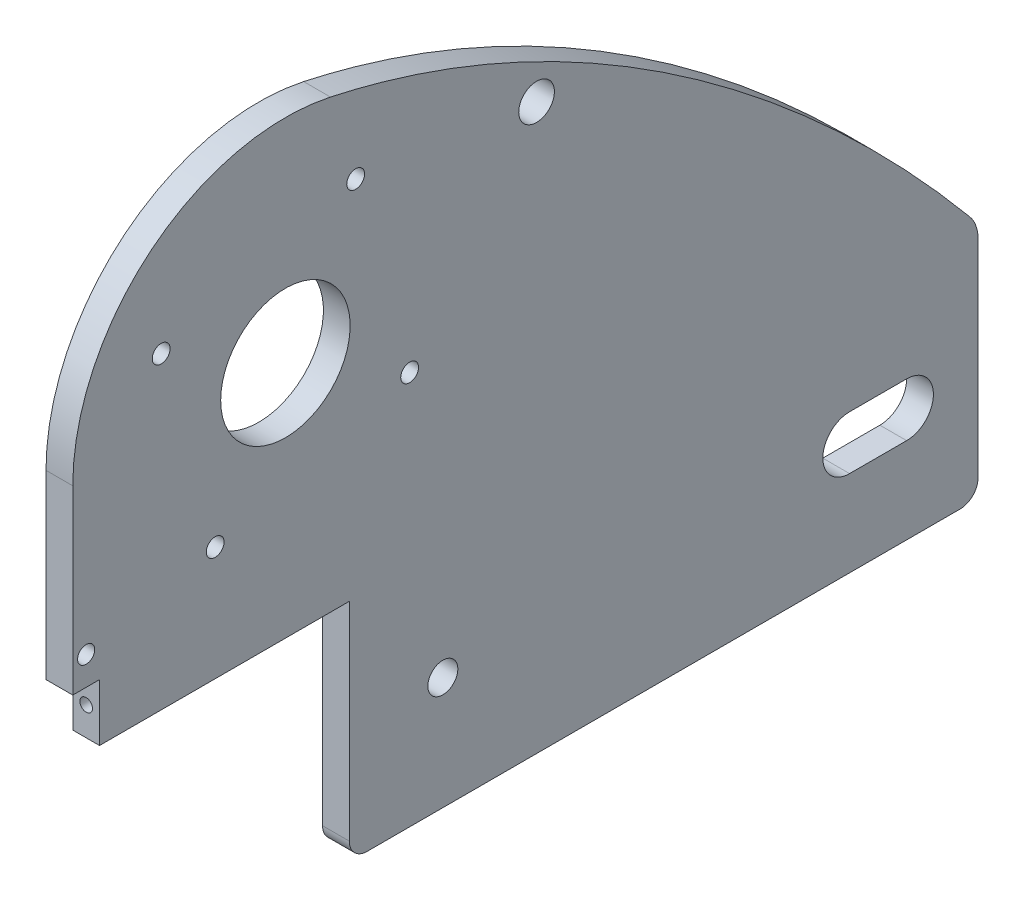
SolidWorks part; units mm, degrees
ref_plane "Front Plane" through (0, 0, 0) normal (0, 0, 1) x (1, 0, 0)
ref_plane "Top Plane" through (0, 0, 0) normal (0, 1, 0) x (1, 0, 0)
ref_plane "Right Plane" through (0, 0, 0) normal (1, 0, 0) x (0, 0, -1)
sketch "Sketch1" plane through (0, 0, 0) normal (1, 0, 0) x (0, 0, -1)
  line L0 (-28.1703, 0) -> (77.3828, 0)
  line L1 (80.5578, 3.175) -> (80.5578, 40.132)
  line L2 (-80.5578, 82.55) -> (-80.5578, 50.292)
  line L4 (-75.7953, 50.292) -> (-75.7953, 40.132)
  line L5 (-80.5578, 50.292) -> (-75.7953, 50.292)
  line L6 (67.8578, 20.066) -> (57.6978, 20.066) construction
  line L7 (-75.7953, 40.132) -> (-31.3453, 40.132)
  line L10 (-31.3453, 40.132) -> (-31.3453, 3.175)
  line L11 (-38.3203, 96.7465) -> (80.2327, 60.1074) construction
  line L12 (-52.6061, 71.4678) -> (39.9396, -11.1914) construction
  line L13 (67.8578, 15.3035) -> (57.6978, 15.3035)
  line L14 (67.8578, 24.8285) -> (57.6978, 24.8285)
  arc A0 (67.8578, 15.3035) -> (67.8578, 24.8285) centre (67.8578, 20.066) ccw
  circle A1 centre (-42.7078, 82.55) radius 31.5 construction
  circle A2 centre (67.8578, 20.066) radius 76.2 construction
  circle A3 centre (67.8578, 20.066) radius 41.91 construction
  circle A4 centre (-42.7078, 82.55) radius 14.859 construction
  arc A5 (-34.6964, 119.5424) -> (-80.5578, 82.55) centre (-42.7078, 82.55) ccw
  arc A6 (-28.1703, 0) -> (-31.3453, 3.175) centre (-28.1703, 3.175) cw
  arc A7 (77.3828, 0) -> (80.5578, 3.175) centre (77.3828, 3.175) ccw
  arc A8 (80.5578, 40.132) -> (79.0888, 44.1938) centre (74.2078, 40.132) ccw
  circle A9 centre (1.9922, 100.457) radius 5.5562 construction
  circle A10 centre (-55.209, 60.4394) radius 1.5875
  circle A11 centre (-14.6922, 20.066) radius 2.667
  circle A12 centre (-20.5972, 70.0488) radius 1.5875
  circle A13 centre (-64.8184, 95.0512) radius 1.5875
  circle A14 centre (-30.2065, 104.6606) radius 1.5875
  circle A15 centre (-78.1765, 55.372) radius 1.524
  circle A16 centre (-42.7078, 82.55) radius 11.5228
  arc A17 (57.6978, 24.8285) -> (57.6978, 15.3035) centre (57.6978, 20.066) ccw
  circle A19 centre (1.9922, 100.457) radius 3.175
  spline S0 degree 3 poles (79.0888, 44.1938) (50.6675, 78.3472) (10.808, 109.6876) (-34.6964, 119.5424) knots 0 0 0 0 1 1 1 1
  point P28 (80.5578, 40.132)
  point P39 (62.7778, 20.066)
  dimension "D4" = 9.525
  dimension "D7" = 29.718
  dimension "D8" = 63
  dimension "D9" = 6.35
  dimension "D12" = 3.175
  dimension "D13" = 6.35
  dimension "D14" = 83.82
  dimension "D15" = 152.4
  dimension "D18" = 5.334
  dimension "D19" = 3.175
  dimension "D20" = 60.325
  dimension "D23" = 3.048
  dimension "D27" = 82.55
  dimension "D28" = 11.1125
  dimension "D2" = 40.132
  dimension "D3" = 20.066
  dimension "D5" = 12.7
  dimension "D6" = 44.45
  dimension "D10" = 127
  dimension "D11" = 95.25
  dimension "D17" = 25.4
  dimension "D21" = 4.7625
  dimension "D22" = 10.16
  dimension "D24" = 5.08
  dimension "D25" = 2.3813
  dimension "D26" = 10.16
  dimension "D16" = 4
extrude "Boss-Extrude1" add sketch "Sketch1" along normal blind 4.7625
sketch "Sketch2" plane through (0, 0, 75.7953) normal (0, 0, 1) x (1, 0, 0)
  line L0 (4.7625, 50.292) -> (4.7625, 40.132) construction
  line L1 (4.7625, 40.132) -> (0, 40.132) construction
  circle A0 centre (2.3813, 45.212) radius 1.1303
  point P4 (4.7625, 45.212)
  point P7 (2.3813, 40.132)
  dimension "D1" = 2.2606
extrude "Cut-Extrude1" cut sketch "Sketch2" against normal blind 6.35
